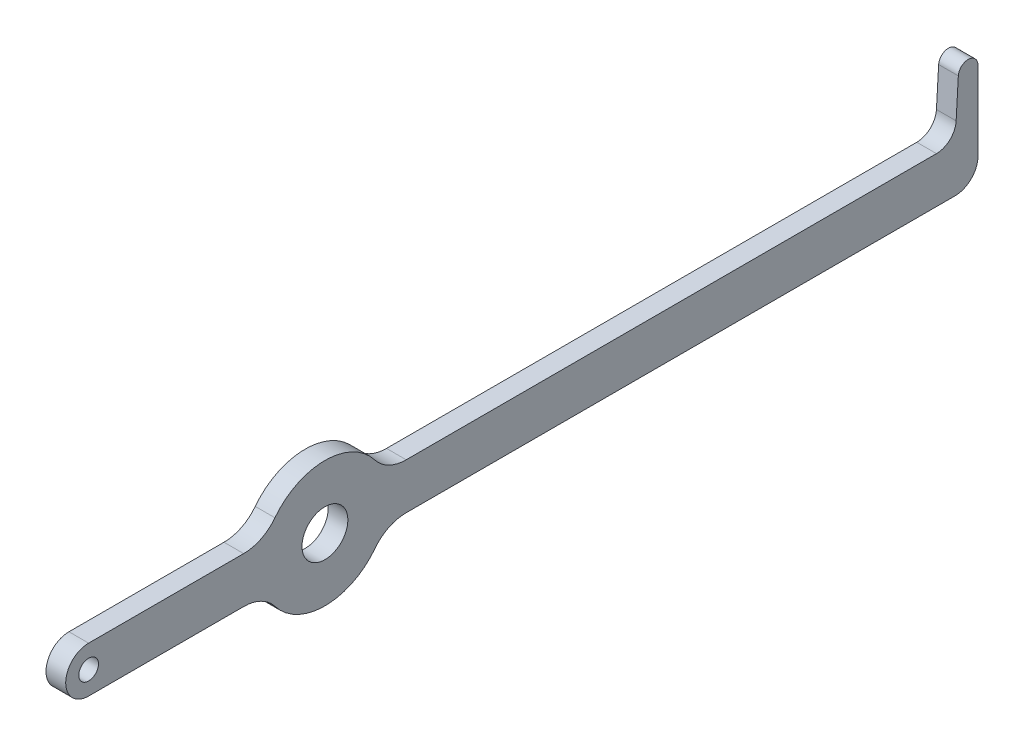
SolidWorks part; units mm, degrees
ref_plane "Front Plane" through (0, 0, 0) normal (0, 0, 1) x (1, 0, 0)
ref_plane "Top Plane" through (0, 0, 0) normal (0, 1, 0) x (1, 0, 0)
ref_plane "Right Plane" through (0, 0, 0) normal (1, 0, 0) x (0, 0, -1)
sketch "Sketch1" plane through (0, 0, 0) normal (1, 0, 0) x (0, 0, -1)
  line L0 (0, 0) -> (-38.1, 0) construction
  line L1 (0, -3.698) -> (-38.1, -3.698)
  line L2 (0, 3.698) -> (-38.1, 3.698)
  line L3 (0, 0) -> (101.6, 0) construction
  line L4 (0, 3.698) -> (101.6, 3.698)
  line L5 (0, -3.698) -> (101.6, -3.698)
  circle A0 centre (0, 0) radius 10.16
  arc A1 (0, -3.698) -> (0, 3.698) centre (0, 0) ccw
  arc A2 (-38.1, 3.698) -> (-38.1, -3.698) centre (-38.1, 0) ccw
  arc A3 (0, 3.698) -> (0, -3.698) centre (0, 0) ccw
  arc A4 (101.6, -3.698) -> (101.6, 3.698) centre (101.6, 0) ccw
  point P4 (-19.05, 0)
  point P9 (50.8, 0)
  dimension "D3" = 20.32
  dimension "D1" = 38.1
  dimension "D2" = 101.6
extrude "Boss-Extrude1" add sketch "Sketch1" along normal mid plane 3.175 contours L2 A2 L1 A0 | A3 L2 A0 L1 | L4 A0 L2 | L1 A0 L5 | A1 L5 A0 L4 | L5 A4 L4 A0 region at (0, -6.3695, 0) region at (0, 0, -6.3723) region at (0, 0, 6.3723) region at (0, 0, 25.478) region at (0, 0, -57.2211) region at (0, 6.3695, 0)
fillet "Fillet1" radius 6.35 4 edges at (0, 3.698, -9.4631) (0, -3.698, -9.4631) (0, -3.698, 9.4631) (0, 3.698, 9.4631)
sketch "Sketch2" plane through (0, 0, 0) normal (1, 0, 0) x (0, 0, -1)
  line L0 (105.298, 0) -> (105.298, 12.7)
  line L1 (13.1003, 3.698) -> (101.6, 3.698) construction
  line L4 (101.6, 3.698) -> (102.1257, 12.7916)
  arc A0 (101.6, -3.698) -> (101.6, 3.698) centre (101.6, 0) ccw construction
  arc A2 (105.298, 12.7) -> (102.1257, 12.7916) centre (103.7105, 12.7) ccw
  arc A3 (105.298, 0) -> (101.6, 3.698) centre (101.6, 0) ccw
  point P5 (0, 0)
  point P6 (101.6, 3.698)
  point P10 (101.4939, 3.698)
  point P13 (105.298, 0)
  dimension "D2" = 1.5875
  dimension "D1" = 12.7
extrude "Boss-Extrude2" add sketch "Sketch2" against normal mid plane 3.175
fillet "Fillet2" radius 3.175 1 edges at (0, 3.698, -101.6)
sketch "Sketch3" plane through (1.5875, 0, 0) normal (1, 0, 0) x (0, 0, -1)
  circle A0 centre (-38.1, 0) radius 1.5875
  dimension "D1" = 3.175
extrude "Cut-Extrude1" cut sketch "Sketch3" against normal through all both and the other way through all
